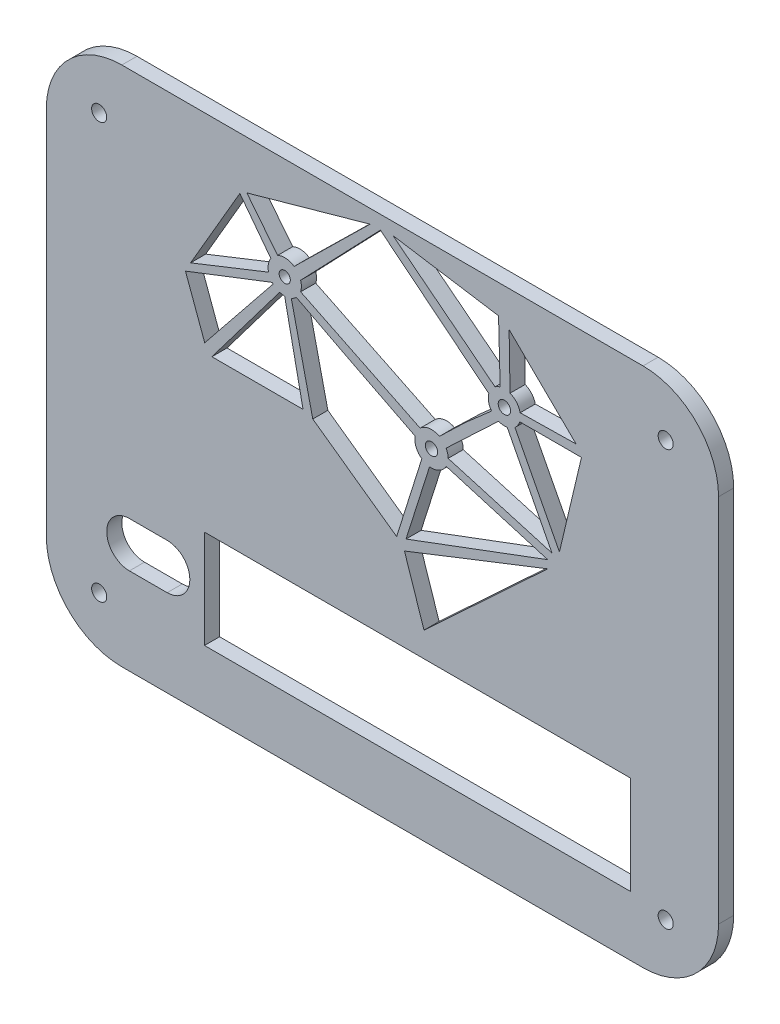
SolidWorks part; units mm, degrees
ref_plane "前视基准面" through (0, 0, 0) normal (0, 0, 1) x (1, 0, 0)
ref_plane "上视基准面" through (0, 0, 0) normal (0, 1, 0) x (1, 0, 0)
ref_plane "右视基准面" through (0, 0, 0) normal (1, 0, 0) x (0, 0, -1)
sketch "草图1" plane through (0, 0, 0) normal (0, 0, 1) x (1, 0, 0)
  line L0 (10, 0) -> (10, -10)
  line L1 (10, 0) -> (79, 0)
  line L2 (0, -10) -> (0, -59)
  line L3 (10, -69) -> (79, -69)
  line L4 (89, -10) -> (89, -59)
  line L5 (10, -10) -> (0, -10)
  line L6 (44.5, 0) -> (44.5, -69) construction
  line L7 (0, -34.5) -> (89, -34.5)
  line L8 (79, -10) -> (89, -10)
  line L9 (79, 0) -> (79, -10)
  line L10 (79, -59) -> (89, -59)
  line L11 (79, -69) -> (79, -59)
  line L12 (10, -59) -> (0, -59)
  line L13 (10, -69) -> (10, -59)
  arc A0 (79, 0) -> (89, -10) centre (79, -10) cw
  arc A1 (0, -59) -> (10, -69) centre (10, -59) ccw
  arc A2 (79, -69) -> (89, -59) centre (79, -59) ccw
  arc A3 (10, 0) -> (0, -10) centre (10, -10) ccw
  circle A4 centre (7, -7) radius 1
  circle A5 centre (82, -7) radius 1
  circle A6 centre (82, -62) radius 1
  circle A7 centre (7, -62) radius 1
  point P7 (89, 0)
  point P10 (0, -69)
  point P15 (0, 0)
  dimension "D3" = 10
  dimension "D5" = 3
  dimension "D6" = 2
  dimension "D1" = 89
  dimension "D2" = 69
  dimension "D4" = 3
extrude "凸台-拉伸1" add sketch "草图1" against normal blind 2 contours L6 L1 L0 L5 L2 L7 | L1 L6 L7 L4 L8 L9 | L6 L7 L2 L12 L13 L3 | L7 L6 L3 L11 L10 L4 | L0 A3 L5 A4 | A0 L9 L8 A5 | L12 A1 L13 A7 | L11 A2 L10 A6 region at (23.4519, -18.1035, 0) region at (5.704, -5.704, 0) region at (65.5481, -18.1035, 0) region at (83.296, -5.704, 0) region at (65.5481, -50.8965, 0) region at (23.4519, -50.8965, 0) region at (5.704, -63.296, 0) region at (83.296, -63.296, 0)
sketch "草图2" plane through (0, 0, 0) normal (0, 0, 1) x (1, 0, 0)
  line L0 (11, -54.5) -> (16, -54.5) construction
  line L1 (11, -51.5) -> (16, -51.5)
  line L2 (11, -57.5) -> (16, -57.5)
  line L3 (10, -69) -> (79, -69) construction
  line L4 (0, -10) -> (0, -59) construction
  arc A0 (11, -51.5) -> (11, -57.5) centre (11, -54.5) ccw
  arc A1 (16, -57.5) -> (16, -51.5) centre (16, -54.5) ccw
  point P2 (13.5, -54.5)
  dimension "D1" = 3
  dimension "D4" = 11
  dimension "D2" = 5
  dimension "D3" = 11.5
extrude "切除-拉伸1" cut sketch "草图2" against normal up to next
sketch "草图3" plane through (0, 0, 0) normal (0, 0, 1) x (1, 0, 0)
  line L1 (20.9383, -48.0843) -> (77.3645, -48.0843)
  line L2 (20.9383, -48.0843) -> (20.9383, -61.0843)
  line L3 (20.9383, -61.0843) -> (77.3645, -61.0843)
  line L4 (77.3645, -48.0843) -> (77.3645, -61.0843)
  dimension "D2" = 13
extrude "切除-拉伸2" cut sketch "草图3" against normal up to next contours L2 L1 L4 L3
sketch "草图4" plane through (0, 0, 0) normal (0, 0, 1) x (1, 0, 0)
  line L0 (25.6244, -6.9111) -> (29.7197, -12.3051)
  line L1 (26.5518, -6.3875) -> (30.6179, -11.5185)
  line L2 (25.6244, -6.9111) -> (19.101, -18.132)
  line L3 (19.101, -18.132) -> (29.4278, -14.0409)
  line L4 (26.5518, -6.3875) -> (42.8576, -1.8193)
  line L5 (42.8576, -1.8193) -> (32.8106, -11.6883)
  line L6 (18.4211, -19.4183) -> (29.9149, -14.9677)
  line L7 (18.4211, -19.4183) -> (20.9713, -26.3652)
  line L8 (20.9713, -26.3652) -> (30.0323, -15.0907)
  line L9 (21.9198, -27.4878) -> (30.8941, -15.6073)
  line L10 (21.9198, -27.4878) -> (33.9876, -27.4878)
  line L11 (33.9876, -27.4878) -> (31.5541, -15.7124)
  line L12 (32.4353, -15.5341) -> (35.2736, -27.9534)
  line L13 (35.2736, -27.9534) -> (46.3811, -35.876)
  line L14 (46.3811, -35.876) -> (49.7127, -25.296)
  line L15 (39.6704, -18.4897) -> (33.1011, -15.0907)
  line L16 (39.6704, -18.4897) -> (48.822, -23.1238)
  line L17 (47.6195, -35.5412) -> (50.7365, -25.691)
  line L18 (47.6195, -35.5412) -> (66.3819, -28.5249)
  line L19 (66.3819, -28.5249) -> (52.9329, -24.5473)
  line L20 (47.4144, -37.0128) -> (66.3819, -29.5739)
  line L21 (66.3819, -29.5739) -> (50.0027, -44.7963)
  line L22 (50.0027, -44.7963) -> (47.4144, -37.0128)
  line L23 (66.9445, -27.4878) -> (53.1964, -23.5024)
  line L24 (66.9445, -27.4878) -> (61.0144, -16.0233)
  line L25 (52.9329, -22.4574) -> (59.8706, -15.9107)
  line L26 (67.9309, -26.8708) -> (62.0387, -15.5341)
  line L27 (67.9309, -26.8708) -> (70.8487, -14.568)
  line L28 (70.8487, -14.568) -> (62.6719, -14.568)
  line L29 (70.1388, -13.3846) -> (62.7281, -13.5081)
  line L30 (70.1388, -13.3846) -> (61.27, -4.6985)
  line L31 (61.27, -4.6985) -> (61.3907, -11.9376)
  line L32 (59.8706, -3.8244) -> (60.0836, -11.8769)
  line L33 (59.8706, -3.8244) -> (45.889, -1.6089)
  line L34 (45.889, -1.6089) -> (59.404, -12.2002)
  line L35 (44.2254, -1.8193) -> (33.6682, -12.8427)
  line L36 (33.6682, -14.1736) -> (49.4921, -21.8888)
  line L37 (55.4908, -18.2369) -> (52.0361, -21.5614)
  line L38 (55.4908, -18.2369) -> (58.9414, -15.2049)
  line L39 (44.2254, -1.8193) -> (58.587, -13.3846)
  circle A0 centre (31.5667, -13.5081) radius 0.7405
  circle A1 centre (31.5667, -13.5081) radius 2.2043
  circle A2 centre (60.6432, -13.9289) radius 0.8201
  circle A3 centre (60.6432, -13.9289) radius 2.127
  circle A4 centre (50.9928, -23.5024) radius 0.8133
  circle A5 centre (50.9928, -23.5024) radius 2.2036
extrude "切除-拉伸3" cut sketch "草图4" against normal up to next contours A1 L5 L4 L1 | A1 L0 L2 L3 | A1 L6 L7 L8 | A1 L9 L10 L11 | A5 L16 L15 A1 L12 L13 L14 | A5 L37 L38 A3 L39 L35 A1 L36 | A3 L32 L33 L34 | A3 L26 L27 L28 | A3 L29 L30 L31 | A5 L23 L24 A3 L25 | A5 L17 L18 L19 | L22 L21 L20 | A0 | A4 | A2 region at (25.0118, -12.8543, 0) region at (33.7443, -6.8715, 0) region at (23.2032, -20.2128, 0) region at (46.461, -12.7307, 0) region at (29.0935, -23.3333, 0) region at (55.2653, -6.0295, 0) region at (41.2348, -25.276, 0) region at (59.9456, -22.0021, 0) region at (64.3651, -10.4475, 0) region at (66.8222, -18.7094, 0) region at (55.1633, -29.4754, 0) region at (54.5997, -37.1277, 0) region at (31.5667, -13.5081, 0) region at (60.6432, -13.9289, 0) region at (50.9928, -23.5024, 0)
